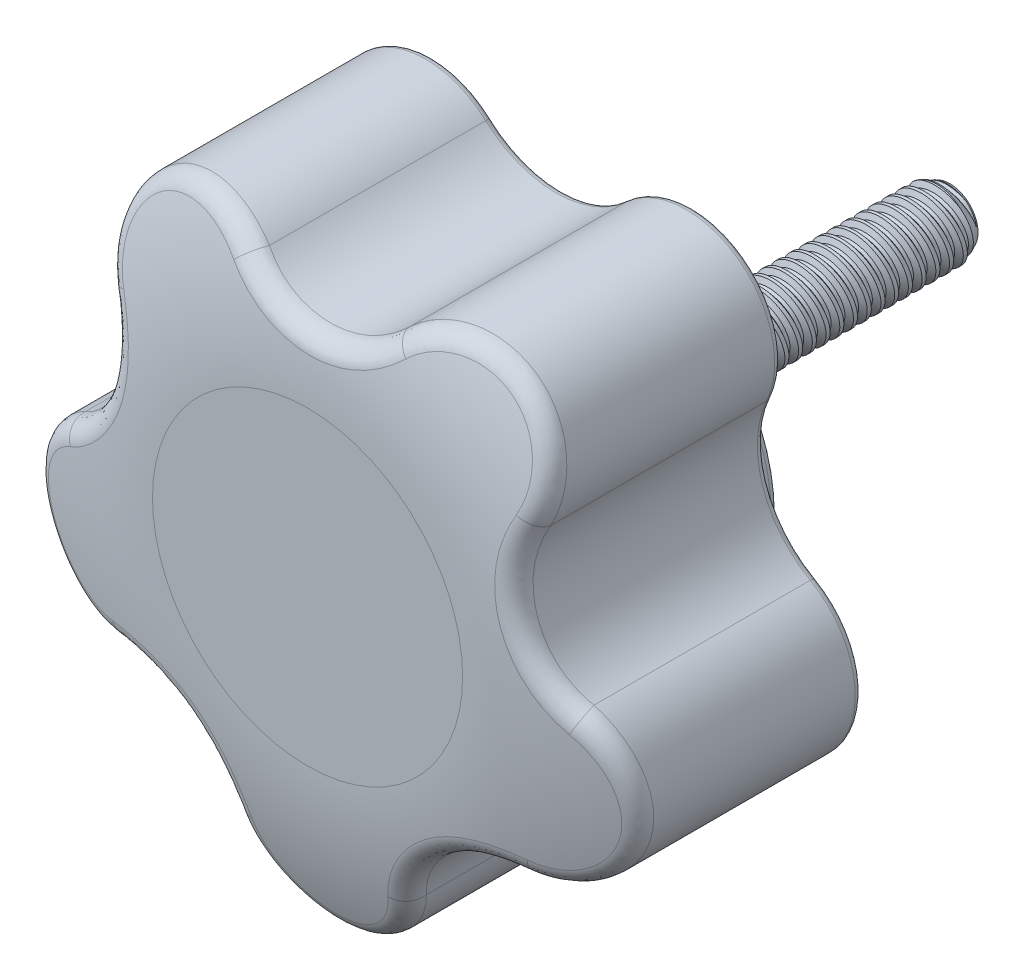
SolidWorks part; units mm, degrees
ref_plane "Front" through (0, 0, 0) normal (0, 0, 1) x (1, 0, 0)
ref_plane "Top" through (0, 0, 0) normal (0, 1, 0) x (1, 0, 0)
ref_plane "Right" through (0, 0, 0) normal (1, 0, 0) x (0, 0, -1)
sketch "Sketch1" plane through (0, 0, 0) normal (1, 0, 0) x (0, 0, -1)
  line L0 (15.875, 0) -> (-15.875, 0)
  line L1 (-15.875, 3.175) -> (-15.875, 4.5339) construction
  line L4 (-15.875, 3.175) -> (15.875, 3.175)
  line L5 (15.875, 3.175) -> (15.875, 0)
  line L6 (-15.875, 0) -> (-15.875, 3.175)
  line L7 (-8.5598, 0) -> (-15.875, 0) construction
  line L10 (-15.875, -3.175) -> (15.875, -3.175) construction
  dimension "Screw Dia" = 6.35
  dimension "Thread Length" = 31.75
revolve "Revolve1" add sketch "Sketch1" angle 360 about L7
sketch "Sketch2" plane through (0, 0, 0) normal (1, 0, 0) x (0, 0, -1)
  line L0 (-15.875, 3.175) -> (-15.875, -3.175) construction
  line L1 (-15.875, -3.175) -> (-14.605, -3.175) construction
  line L2 (-14.605, -3.175) -> (-15.875, 3.175) construction
  line L3 (-15.875, 3.175) -> (-15.7193, 3.2061) construction
  line L4 (-15.7193, 3.2061) -> (-14.6297, 3.4241)
  line L5 (-14.6297, 3.4241) -> (-14.884, 2.6722)
  line L6 (-14.884, 2.6722) -> (-15.1954, 2.6099)
  line L7 (-15.1954, 2.6099) -> (-15.7193, 3.2061)
  line L8 (-15.0397, 2.641) -> (-15.1745, 3.3151) construction
  line L9 (-15.875, 3.175) -> (-15.1465, 3.175) construction
  line L10 (-15.1465, 3.175) -> (-13.8765, -3.175) construction
  line L11 (-13.8765, -3.175) -> (-14.605, -3.175) construction
  line L12 (-15.875, -3.175) -> (15.875, -3.175) construction
  line L13 (-15.875, 3.175) -> (15.875, 3.175) construction
  line L14 (-15.875, 0) -> (-15.875, 3.175) construction
  line L15 (-15.875, -0.2727) -> (-13.148, 0.2727) construction
  point P19 (-14.5115, 0)
  dimension "D1" = 0.1588
  dimension "D2" = 0.3175
  dimension "D3" = 60
  dimension "Thread Pitch" = 1.27
  dimension "D4" = 1.27
revolve "Cut-Revolve1" cut sketch "Sketch2" angle 360 about L15
pattern_linear "LPattern1" count 25 spacing 1.27 along (0, 0, -1) count 2 spacing 1.27 along (0, 0, 1) of "Cut-Revolve1"
sketch "Sketch5" plane through (0, 0, 0) normal (1, 0, 0) x (0, 0, -1)
  line L0 (-15.875, 0) -> (28.575, 0) construction
  line L2 (-15.875, 15.875) -> (-19.939, 15.875)
  line L3 (-19.939, 15.875) -> (-19.939, 28.702)
  line L4 (-15.875, 0) -> (-15.875, -15.875) construction
  line L5 (-15.875, 15.875) -> (-15.875, 0)
  line L7 (-43.561, 0) -> (-15.875, 0)
  line L12 (-43.561, 28.702) -> (-19.939, 28.702)
  line L13 (-43.561, 28.702) -> (-43.561, 0)
  line L14 (-19.939, -15.875) -> (-19.939, -28.702) construction
  dimension "D1" = 28.702
  dimension "D" = 4.064
  dimension "B" = 31.75
  dimension "C" = 23.622
  dimension "A" = 57.404
revolve "Revolve3" add sketch "Sketch5" angle 360 about L0
ref_plane "Plane1" through (0, 0, 43.561) normal (0, 0, 1) x (1, 0, 0)
sketch "Sketch6" plane through (0, 0, 43.561) normal (0, 0, 1) x (1, 0, 0)
  line L0 (0, 0) -> (0, 32.6984) construction
  line L1 (0, 0) -> (31.0981, 10.1044) construction
  line L2 (0, 0) -> (16.8706, 23.2204) construction
  line L4 (0, 32.6984) -> (0, 20.0914)
  line L5 (19.1081, 6.2086) -> (31.0981, 10.1044)
  arc A2 (19.5081, 13.1779) -> (19.1081, 6.2086) centre (28.2528, 9.1799) ccw
  circle A3 centre (0, 0) radius 28.702 construction
  arc A4 (31.0981, 10.1044) -> (0, 32.6984) centre (0, 0) ccw
  circle A5 centre (0, 0) radius 20.0914 construction
  arc A6 (16.8706, 23.2204) -> (6.5046, 22.6255) centre (12.0513, 16.5871) ccw
  arc A7 (16.8706, 23.2204) -> (19.5081, 13.1779) centre (12.0513, 16.5871) cw
  arc A8 (0, 20.0914) -> (6.5046, 22.6255) centre (0, 29.7067) ccw
  dimension "D2" = 40.1828
  dimension "D3" = 36
  dimension "D4" = 16.0731
  dimension "D1" = 72
extrude "Cut-Extrude1" cut sketch "Sketch6" against normal through all
pattern_circular "CirPattern1" count 5 over 360 of "Cut-Extrude1"
sketch "Sketch8" plane through (0, 0, 0) normal (1, 0, 0) x (0, 0, -1)
  line L0 (-43.561, 28.702) -> (-43.561, 0) construction
  line L2 (-43.561, 28.702) -> (-19.939, 28.702) construction
  line L3 (-40.386, 28.702) -> (-40.386, 29.972)
  line L5 (-40.386, 29.972) -> (-44.831, 29.972)
  line L6 (-15.875, 0) -> (-43.561, 0) construction
  line L8 (-44.831, 29.972) -> (-44.831, 14.351)
  line L9 (-44.831, 14.351) -> (-43.561, 14.351)
  line L10 (-43.561, 0) -> (-43.561, 32.6984) construction
  arc A0 (-43.561, 14.351) -> (-40.386, 28.702) centre (-9.5402, 14.351) cw
  dimension "D1" = 3.175
  dimension "D2" = 1.27
  dimension "D3" = 1.27
revolve "Cut-Revolve3" cut sketch "Sketch8" angle 360 about L6
fillet "Fillet4" radius 0.635 5 edges at (16.8706, 23.2204, 19.939) (19.1081, 6.2086, 19.939) (-16.8706, 23.2204, 19.939) (15.875, 0, 15.875) (0, 20.0914, 19.939)
sketch "Sketch7" plane through (0, 0, 0) normal (1, 0, 0) x (0, 0, -1)
  line L0 (15.875, 2.6099) -> (14.6632, 3.175)
  line L1 (15.875, 3.175) -> (15.875, 0) construction
  line L2 (-15.875, 3.175) -> (15.875, 3.175) construction
  line L3 (14.6632, 3.175) -> (15.875, 3.175)
  line L4 (15.875, 3.175) -> (15.875, 2.6099)
  line L6 (28.575, 0) -> (15.875, 0) construction
  dimension "D1" = 25
revolve "Cut-Revolve2" cut sketch "Sketch7" angle 360 about L6
fillet "Fillet5" radius 1.905 3 edges at (-0.9206, 20.1356, 43.062) (18.8656, 7.0978, 43.062) (16.9041, 23.1959, 40.386)
combine bodies "Combine1" operation type add bodies to combine 151 150
sketch "Sketch9" plane through (0, 0, 15.875) normal (0, 0, -1) x (-1, 0, 0)
  circle A0 centre (0, 0) radius 15.875 construction
  circle A1 centre (0, 0) radius 15.875
sketch "Sketch10" plane through (0, 0, 0) normal (0, 0, 1) x (1, 0, 0)
  circle A0 centre (0, 0) radius 28.702
  arc A1 (-6.5046, 22.6255) -> (-19.5081, 13.1779) centre (-12.0513, 16.5871) ccw construction
equation "\"D1@Sketch2\"=\"Thread Pitch@Sketch2\"/8"
equation "\"D2@Sketch2\"=\"Thread Pitch@Sketch2\"/4"
equation "\"D4@Sketch2\"=\"Thread Pitch@Sketch2\""
equation "\"D3@LPattern1\"=\"Thread Pitch@Sketch2\""
equation "\"D4@LPattern1\"=\"Thread Pitch@Sketch2\""
equation "\"D1@LPattern1\"=\"Thread Length@Sketch1\"/\"Thread Pitch@Sketch2\""
equation "\"D2@Sketch6\" = \"A@Sketch5\"*.7"
equation "\"D1@Sketch5\" = \"A@Sketch5\"/2"
equation "\"D4@Sketch6\" = \"D2@Sketch6\"/2.5"
